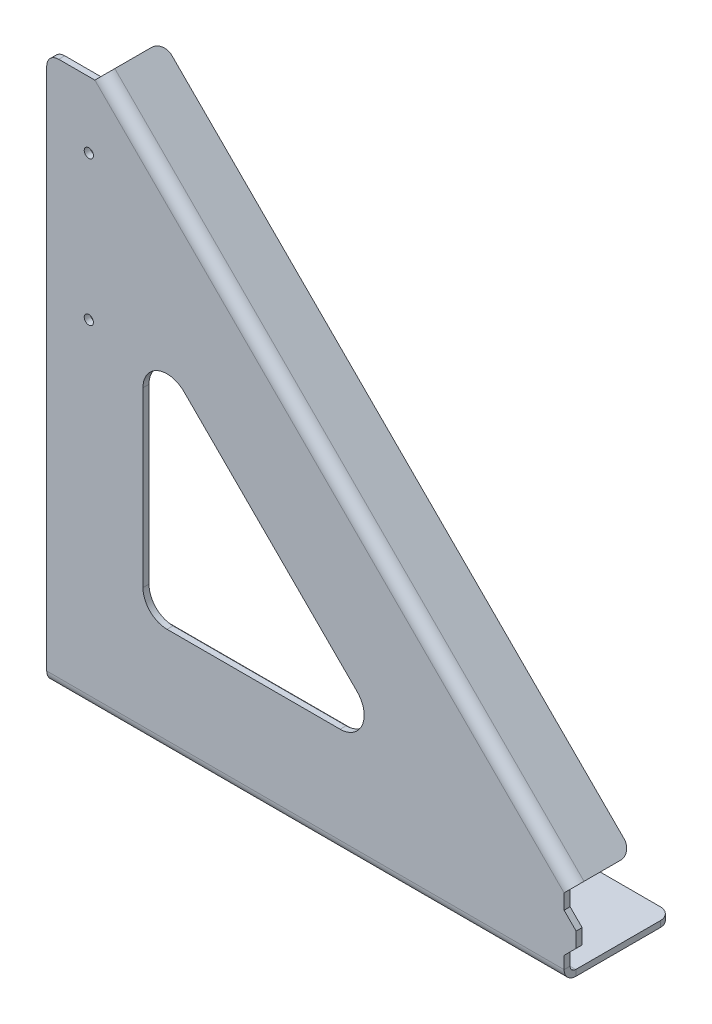
SolidWorks part; units mm, degrees
note: The reader was unsure of these and kept them because the rebuilt part matched: flange length of "Edge-Flange1", "Edge-Flange2".
ref_plane "Front Plane" through (0, 0, 0) normal (0, 0, 1) x (1, 0, 0)
ref_plane "Top Plane" through (0, 0, 0) normal (0, 1, 0) x (1, 0, 0)
ref_plane "Right Plane" through (0, 0, 0) normal (1, 0, 0) x (0, 0, -1)
sketch "Sketch1" plane through (0, 0, 0) normal (0, 0, 1) x (1, 0, 0)
  line L0 (0, 0) -> (273.05, 0)
  line L1 (273.05, 0) -> (273.05, 41.275)
  line L2 (273.05, 41.275) -> (25.4, 288.925)
  line L3 (25.4, 288.925) -> (0, 288.925)
  line L4 (0, 288.925) -> (0, 0)
  dimension "D1" = 41.275
  dimension "D2" = 273.05
  dimension "D3" = 25.4
  dimension "D4" = 45
base flange "Base-Flange1" sketch "Sketch1" thickness 3.175 reverse thickness direction no parameters "D1"=3
edge flange "Edge-Flange1" sketch "Sketch8" flange angle 90 flange length 31.75 flange position bend outside bend radius 3 thickness 3.175 relief rectangular parameters "D6"=10
sketch "Sketch8" plane through (157.1625, 157.1625, -3.175) normal (-0.7071, -0.7071, 0) x (-0.7071, 0.7071, 0)
  line L2 (-163.8897, 0) -> (-163.8897, 28.575)
  line L3 (-163.8897, 28.575) -> (186.3403, 28.575)
  line L4 (186.3403, 28.575) -> (186.3403, 0)
  line L5 (186.3403, 0) -> (-163.8897, 0) construction
  line L6 (186.3403, 0) -> (-163.8897, 0)
bend "EdgeBend1" bend radius 3 bend angle 90 parameters "D5"=1
edge flange "Edge-Flange2" sketch "Sketch11" flange angle 90 flange length 57.15 flange position material inside bend radius 3 thickness 3.175 relief rectangular parameters "D6"=10
sketch "Sketch11" plane through (0, 0, -3.175) normal (0, 1, 0) x (1, 0, 0)
  line L2 (0, 0) -> (0, 53.975)
  line L3 (0, 53.975) -> (273.05, 53.975)
  line L4 (273.05, 53.975) -> (273.05, 0)
  line L5 (273.05, 0) -> (0, 0) construction
  line L6 (273.05, 0) -> (0, 0)
bend "EdgeBend2" bend radius 3 bend angle 90 parameters "D5"=2
sketch "Sketch12" plane through (0, 0, 0) normal (0, 0, 1) x (1, 0, 0)
  line L0 (50.8, 191.683) -> (50.8, 56.975)
  line L1 (185.508, 56.975) -> (50.8, 56.975)
  line L2 (50.8, 191.683) -> (185.508, 56.975)
  line L3 (273.05, 41.275) -> (25.4, 288.925) construction
  line L4 (0, 6.175) -> (273.05, 6.175) construction
  line L5 (0, 288.925) -> (0, 6.175) construction
  dimension "D1" = 50.8
  dimension "D2" = 50.8
  dimension "D3" = 50.8
extrude "Cut-Extrude1" cut sketch "Sketch12" against normal through all normal cut yes
fillet "Fillet1" radius 12.7 3 edges at (50.8, 191.683, -1.5875) (50.8, 56.975, -1.5875) (185.508, 56.975, -1.5875)
hole_wizard "#11 (0.191) Diameter Hole1" positions "Sketch13" profile "Sketch14" hole size "#11" standard "ANSI Inch" end condition through all
sketch "Sketch13" plane through (0, 0, -3.175) normal (0, 0, -1) x (-1, 0, 0)
  line L0 (0, 288.925) -> (0, 6.175) construction
  line L1 (-273.05, 0) -> (0, 0) construction
  point P0 (-22.225, 254)
  point P2 (-22.225, 177.8)
  dimension "D1" = 22.225
  dimension "D2" = 76.2
  dimension "D3" = 177.8
sketch "Sketch14" plane through (22.225, 254, -3.175) normal (1, 0, 0) x (0, 1, 0)
  line L0 (0, 0) -> (0, 3.175)
  line L1 (0, 3.175) -> (2.4257, 3.175)
  line L2 (2.4257, 3.175) -> (2.4257, 0)
  line L5 (2.4257, 0) -> (0, 0)
  line L11 (0, -6.35) -> (0, 107.95) construction
  dimension "Thru Hole Dia." = 4.8514
  dimension "Thru Hole Depth" = 3.175
sketch "Sketch15" plane through (0, 0, 0) normal (0, 0, 1) x (1, 0, 0)
  line L0 (273.05, 33.3375) -> (279.4, 26.9875)
  line L1 (273.05, 6.175) -> (273.05, 41.275) construction
  line L2 (279.4, 26.9875) -> (279.4, 19.05)
  line L3 (279.4, 19.05) -> (273.05, 12.7)
  line L4 (273.05, 33.3375) -> (273.05, 12.7)
  line L5 (273.05, 0) -> (0, 0) construction
  dimension "D1" = 45
  dimension "D2" = 45
  dimension "D3" = 6.35
  dimension "D4" = 33.3375
  dimension "D5" = 12.7
extrude "Boss-Extrude1" add sketch "Sketch15" against normal up to surface (3.175 mm away) up to face at (19.7993, 254, -3.175)
fillet "Fillet2" radius 6.35 5 edges at (0, 288.925, -1.5875) (28.6439, 292.1689, -31.75) (0, 1.5875, -57.15) (273.05, 1.5875, -57.15) (276.2939, 44.5189, -31.75)
sketch "Bend-Lines1" [suppressed] plane through (0, 0, 0) normal (0, 1, 0) x (1, 0, 0)
sketch "Bounding-Box1" [suppressed] plane through (0, 0, 0) normal (0, 1, 0) x (1, 0, 0)
sheet metal parameters "Sheet-Metal1" thickness 3.175 parameters "D1"=3
flat pattern "Flat-Pattern1" [suppressed]
sketch "Bend-Lines2" plane through (0, 0, 0) normal (0, 1, 0) x (1, 0, 0)
sketch3d "Bounding-Box2" [suppressed]
  line L0 (-301.625, 333.375, 0) -> (-301.625, 0, 0) construction
  line L1 (0, 333.375, 0) -> (0, 0, 0) construction
  line L2 (-301.625, 333.375, 0) -> (0, 333.375, 0) construction
  line L3 (-301.625, 0, 0) -> (0, 0, 0) construction
sheet metal parameters "Sheet-Metal2" thickness 3.175 parameters "D1"=3
flat pattern "Flat-Pattern1"
sketch "Bend-Lines2" plane through (0, 0, 0) normal (0, 0, 1) x (1, 0, 0)
  line L0 (304.1727, 46.9977) -> (27.9477, 323.2227) construction
  line L1 (304.1727, 46.9977) -> (27.9477, 323.2227) construction
sketch3d "Bounding-Box2" [suppressed]
  line L0 (324.8047, 343.8547, 0) -> (324.8047, 0, 0) construction
  line L1 (0, 343.8547, 0) -> (0, 0, 0) construction
  line L2 (324.8047, 343.8547, 0) -> (0, 343.8547, 0) construction
  line L3 (324.8047, 0, 0) -> (0, 0, 0) construction
bend of the flat pattern "Flatten-<EdgeBend1>1"
sheet metal parameters "Sheet-Metal3" thickness 3.175 parameters "D1"=3
flat pattern "Flat-Pattern1"
sketch "Bend-Lines2" plane through (0, 0, 0) normal (0, 0, 1) x (1, 0, 0)
  line L0 (304.1727, 46.9977) -> (27.9477, 323.2227) construction
  line L1 (304.1727, 46.9977) -> (27.9477, 323.2227) construction
  line L2 (0, 2.572) -> (301.625, 2.572) construction
  line L3 (0, 2.572) -> (301.625, 2.572) construction
sketch3d "Bounding-Box2" [suppressed]
  line L0 (324.8047, 343.8547, 0) -> (324.8047, -52.006, 0) construction
  line L1 (0, 343.8547, 0) -> (0, -52.006, 0) construction
  line L2 (324.8047, 343.8547, 0) -> (0, 343.8547, 0) construction
  line L3 (324.8047, -52.006, 0) -> (0, -52.006, 0) construction
bend of the flat pattern "Flatten-<EdgeBend1>1"
bend of the flat pattern "Flatten-<EdgeBend2>1"
sheet metal parameters "Sheet-Metal4" thickness 3.175 parameters "D1"=3
flat pattern "Flat-Pattern1"
sketch "Bend-Lines2" plane through (0, 0, 0) normal (0, 0, 1) x (1, 0, 0)
  line L0 (275.5977, 40.6477) -> (27.9477, 288.2977) construction
  line L1 (275.5977, 40.6477) -> (27.9477, 288.2977) construction
  line L2 (0, 2.572) -> (273.05, 2.572) construction
  line L3 (0, 2.572) -> (273.05, 2.572) construction
sketch3d "Bounding-Box2" [suppressed]
  line L0 (296.2297, 308.9297, 0) -> (296.2297, -52.006, 0) construction
  line L1 (0, 308.9297, 0) -> (0, -52.006, 0) construction
  line L2 (296.2297, 308.9297, 0) -> (0, 308.9297, 0) construction
  line L3 (296.2297, -52.006, 0) -> (0, -52.006, 0) construction
bend of the flat pattern "Flatten-<EdgeBend1>1"
bend of the flat pattern "Flatten-<EdgeBend2>1"
sheet metal parameters "Sheet-Metal5" thickness 3.175 parameters "D1"=3
flat pattern "Flat-Pattern1"
sketch "Bend-Lines2" plane through (0, 0, 0) normal (0, 0, 1) x (1, 0, 0)
  line L0 (275.5977, 43.8227) -> (27.9477, 291.4727) construction
  line L1 (275.5977, 43.8227) -> (27.9477, 291.4727) construction
  line L2 (0, 2.572) -> (273.05, 2.572) construction
  line L3 (0, 2.572) -> (273.05, 2.572) construction
sketch3d "Bounding-Box2" [suppressed]
  line L0 (296.2297, 312.1047, 0) -> (296.2297, -52.006, 0) construction
  line L1 (0, 312.1047, 0) -> (0, -52.006, 0) construction
  line L2 (296.2297, 312.1047, 0) -> (0, 312.1047, 0) construction
  line L3 (296.2297, -52.006, 0) -> (0, -52.006, 0) construction
bend of the flat pattern "Flatten-<EdgeBend1>1"
bend of the flat pattern "Flatten-<EdgeBend2>1"
sheet metal parameters "Sheet-Metal6" thickness 3.175 parameters "D1"=3
flat pattern "Flat-Pattern1"
sketch "Bend-Lines2" plane through (0, 0, 0) normal (0, 0, 1) x (1, 0, 0)
  line L0 (275.5977, 43.8227) -> (27.9477, 291.4727) construction
  line L1 (275.5977, 43.8227) -> (27.9477, 291.4727) construction
  line L2 (0, 2.572) -> (273.05, 2.572) construction
  line L3 (0, 2.572) -> (273.05, 2.572) construction
sketch3d "Bounding-Box2" [suppressed]
  line L0 (293.5994, 309.4744, 0) -> (293.5994, -52.006, 0) construction
  line L1 (0, 309.4744, 0) -> (0, -52.006, 0) construction
  line L2 (293.5994, 309.4744, 0) -> (0, 309.4744, 0) construction
  line L3 (293.5994, -52.006, 0) -> (0, -52.006, 0) construction
bend of the flat pattern "Flatten-<EdgeBend1>1"
bend of the flat pattern "Flatten-<EdgeBend2>1"
